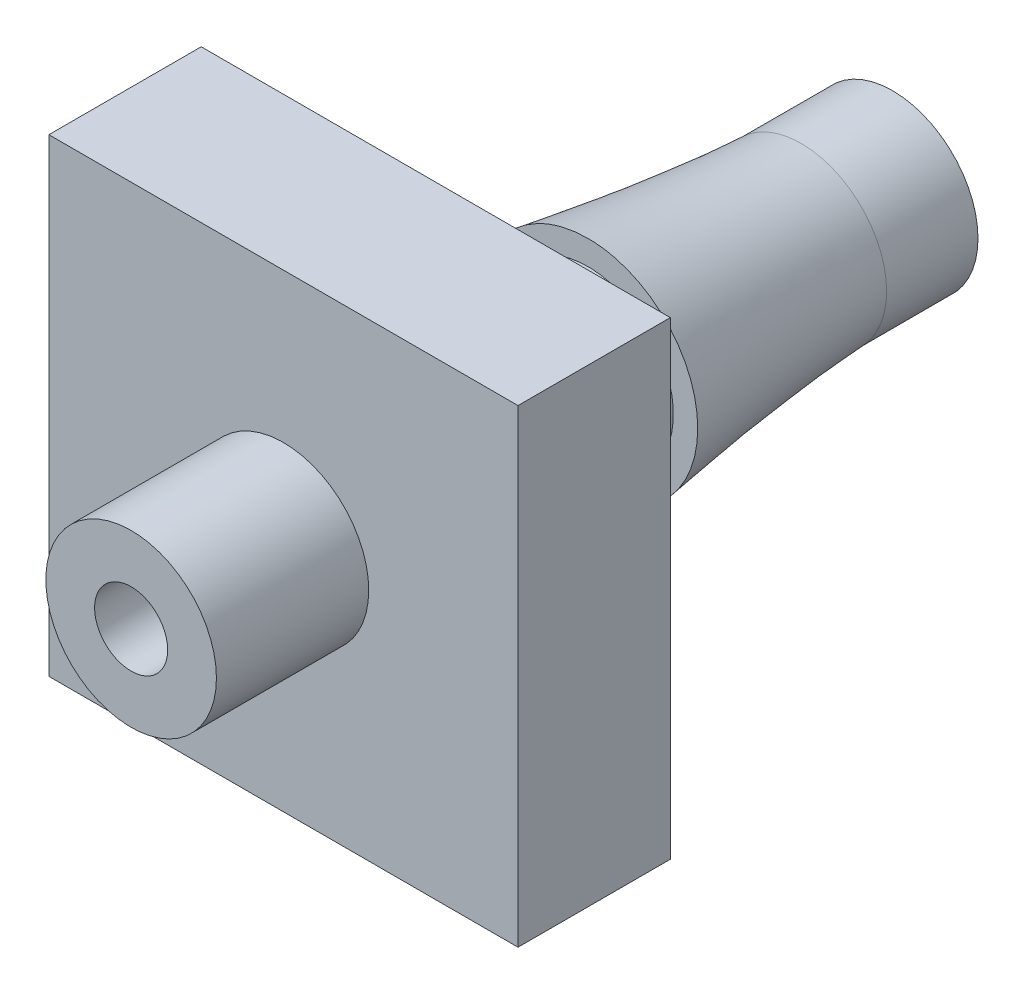
SolidWorks part; units mm, degrees
ref_plane "Alzado" through (0, 0, 0) normal (0, 0, 1) x (1, 0, 0)
ref_plane "Planta" through (0, 0, 0) normal (0, 1, 0) x (1, 0, 0)
ref_plane "Vista lateral" through (0, 0, 0) normal (1, 0, 0) x (0, 0, -1)
sketch "Croquis1" plane through (0, 0, 0) normal (0, 0, 1) x (1, 0, 0)
  line L1 (-3.85, -3.85) -> (3.85, -3.85)
  line L2 (-3.85, -3.85) -> (-3.85, 3.85)
  line L3 (-3.85, 3.85) -> (3.85, 3.85)
  line L4 (3.85, -3.85) -> (3.85, 3.85)
  line L5 (-3.85, -3.85) -> (3.85, 3.85) construction
  line L6 (-3.85, 3.85) -> (3.85, -3.85) construction
  point P0 (0, 0)
  dimension "D1" = 7.7
  dimension "D2" = 7.7
extrude "Saliente-Extruir1" add sketch "Croquis1" along normal blind 2.5
sketch "Croquis2" plane through (0, 0, 0) normal (0, 0, -1) x (-1, 0, 0)
  circle A0 centre (0, 0) radius 1.4
  dimension "D1" = 2.8
extrude "Saliente-Extruir2" add sketch "Croquis2" along normal blind 7.5
ref_plane "Plano1" through (0, 0, -2.5) normal (0, 0, -1) x (-1, 0, 0)
sketch "Croquis3" plane through (0, 0, -2.5) normal (0, 0, -1) x (-1, 0, 0)
  circle A0 centre (0, 0) radius 1.8
  dimension "D1" = 3.6
ref_plane "Plano2" through (0, 0, 1.25) normal (0, 0, -1) x (-1, 0, 0)
ref_plane "Plano3" through (0, 0, -6) normal (0, 0, -1) x (-1, 0, 0)
sketch "Croquis5" plane through (0, 0, -6) normal (0, 0, -1) x (-1, 0, 0)
  circle A0 centre (0, 0) radius 1.4
loft "Recubrir2" add profiles "Croquis3", "Croquis5" connector at (-0.3384, 1.7679, -2.5) connector at (-0.8678, 1.0986, -6)
sketch "Croquis7" plane through (0, 0, 2.5) normal (0, 0, 1) x (1, 0, 0)
  circle A0 centre (0, 0) radius 1.4
  dimension "D1" = 2.8
extrude "Saliente-Extruir3" add sketch "Croquis7" along normal blind 2.5
sketch "Croquis6" plane through (0, 0, -7.5) normal (0, 0, -1) x (-1, 0, 0)
  circle A0 centre (0, 0) radius 0.6
  dimension "D1" = 1.2
extrude "Cortar-Extruir1" cut sketch "Croquis6" against normal through all
